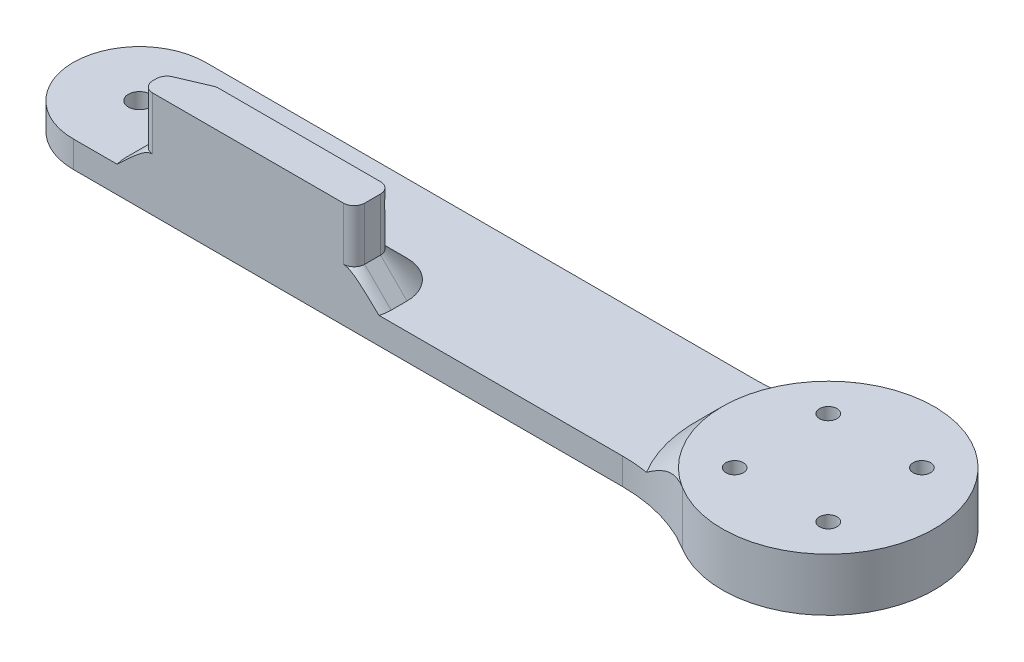
SolidWorks part; units mm, degrees
ref_plane "前视基准面" through (0, 0, 0) normal (0, 0, 1) x (1, 0, 0)
ref_plane "上视基准面" through (0, 0, 0) normal (0, 1, 0) x (1, 0, 0)
ref_plane "右视基准面" through (0, 0, 0) normal (1, 0, 0) x (0, 0, -1)
sketch "草图1" plane through (0, 0, 0) normal (0, 1, 0) x (1, 0, 0)
  line L0 (-65, 0) -> (65, 0) construction
  line L1 (-65, 12.5) -> (65, 12.5)
  line L2 (-65, -12.5) -> (65, -12.5)
  arc A0 (-65, 12.5) -> (-65, -12.5) centre (-65, 0) ccw
  arc A1 (65, -12.5) -> (65, 12.5) centre (65, 0) ccw
  point P2 (0, 0)
  dimension "D2" = 12.5
  dimension "D1" = 130
extrude "凸台-拉伸1" add sketch "草图1" along normal blind 5
sketch "草图7" plane through (0, 0, 0) normal (0, 1, 0) x (1, 0, 0)
  circle A0 centre (65, 0) radius 20
  dimension "D1" = 40
extrude "凸台-拉伸3" add sketch "草图7" along normal blind 10
sketch "草图8" plane through (0, 10, 0) normal (0, 1, 0) x (1, 0, 0)
  line L0 (65, 0) -> (56.1612, 8.8388) construction
  line L1 (52.5, 0) -> (65, 0) construction
  line L2 (65, 0) -> (56.1612, 8.8388) construction
  circle A5 centre (65, 0) radius 12.5 construction
  circle A6 centre (56.1612, 8.8388) radius 1.65
  circle A7 centre (73.8388, 8.8388) radius 1.65
  circle A8 centre (73.8388, -8.8388) radius 1.65
  circle A9 centre (56.1612, -8.8388) radius 1.65
  dimension "D1" = 25
  dimension "D2" = 45
  dimension "D3" = 3.3
  dimension "D4" = 4
extrude "切除-拉伸2" cut sketch "草图8" against normal up to next
sketch "草图9" plane through (0, 5, 0) normal (0, 1, 0) x (1, 0, 0)
  circle A0 centre (-65, 0) radius 2.1
  dimension "D1" = 4.2
extrude "切除-拉伸3" cut sketch "草图9" against normal up to next
sketch "草图10" plane through (0, 5, 0) normal (0, 1, 0) x (1, 0, 0)
  line L0 (-65, -12.5) -> (49.3875, -12.5) construction
  line L1 (-52, -12.5) -> (-12, -12.5)
  line L2 (-52, -12.5) -> (-52, -5.5)
  line L3 (-52, -5.5) -> (-12, -5.5)
  line L4 (-12, -12.5) -> (-12, -5.5)
  dimension "D3" = 13
  dimension "D1" = 40
  dimension "D2" = 7
extrude "凸台-拉伸4" add sketch "草图10" along normal blind 15
chamfer "倒角1" distance 7 distance2 3 1 edges at (-52, 12.5, 5.5) first distance on face at (-32, 12.5, 5.5)
sketch "草图11" plane through (-52, 0, 0) normal (-1, 0, 0) x (0, 0, 1)
  line L0 (5.5, 17.5) -> (4.5, 17.5) construction
  line L1 (5.5, 5) -> (5.5, 20) construction
  line L2 (5.5, 20) -> (8.5, 20) construction
  circle A0 centre (4.5, 17.5) radius 2
  dimension "D2" = 4
  dimension "D1" = 1
  dimension "D3" = 2.5
extrude "切除-拉伸4" cut sketch "草图11" against normal up to next
fillet "圆角2" radius 2 6 edges at (-52, 12.5, 8.5) (-52, 12.5, 12.5) (-45, 10.384, 5.5) (-45, 19.616, 5.5) (-12, 10.384, 5.5) (-12, 12.5, 12.5)
chamfer "倒角2" distance 5 angle 45 9 edges at (-51.4142, 5, 11.9142) (-52, 5, 10.1594) (-51.6697, 5, 8.7178) (-48.0826, 5, 6.8211) (-44.9916, 5, 5.5408) (-29.2947, 5, 5.5) (-12.5858, 5, 6.0858) (-12, 5, 9) (-12.5858, 5, 11.9142)
sketch "草图12" plane through (0, 20, 0) normal (0, 1, 0) x (1, 0, 0)
  line L0 (-61.3333, -12.5) -> (-33.3333, -0.5)
  line L1 (-65, -12.5) -> (-56.7082, -12.5) construction
  line L2 (-44.5895, -0.5) -> (-14, -0.5) construction
  line L3 (-45.3773, -5.6617) -> (-50.7878, -7.9805) construction
  line L4 (-61.3333, -12.5) -> (-61.3333, -0.5)
  line L5 (-61.3333, -0.5) -> (-33.3333, -0.5)
extrude "切除-拉伸5" cut sketch "草图12" against normal up to surface (15 mm away) up to face at (-65, 5, 2.1)
fillet "圆角3" radius 30 2 edges at (49.3875, 2.5, 12.5) (49.3875, 2.5, -12.5)
chamfer "倒角3" distance 5 angle 45 1 edges at (45, 5, 0)
